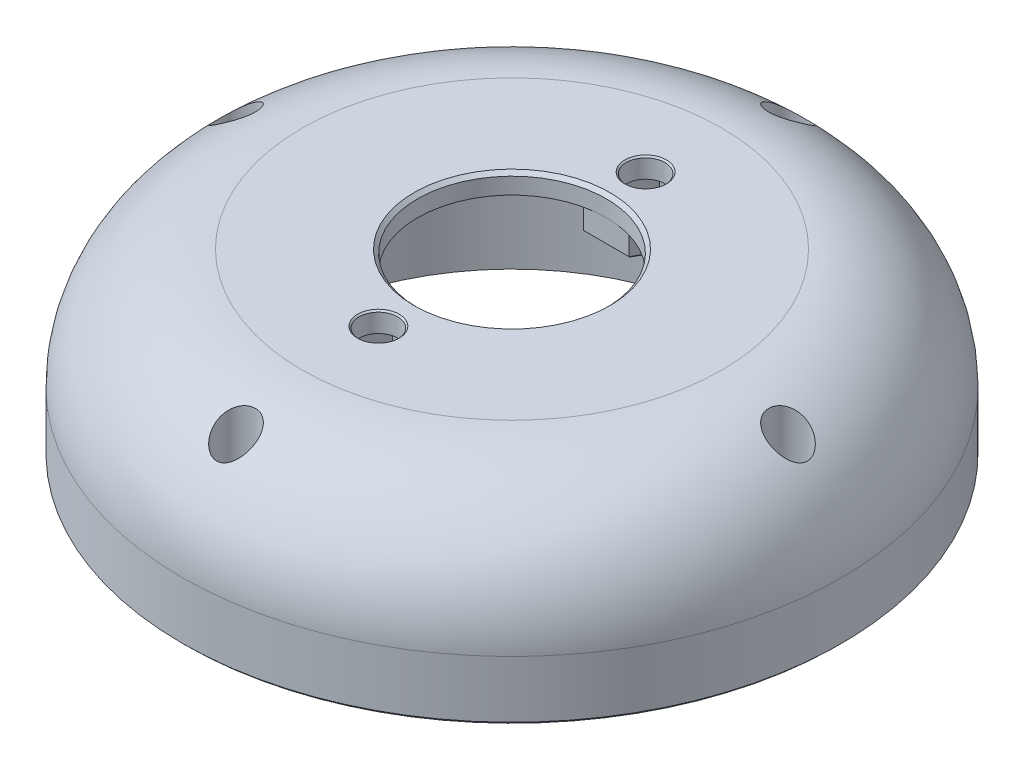
SolidWorks part; units mm, degrees
ref_plane "Front Plane" through (0, 0, 0) normal (0, 0, 1) x (1, 0, 0)
ref_plane "Top Plane" through (0, 0, 0) normal (0, 1, 0) x (1, 0, 0)
ref_plane "Right Plane" through (0, 0, 0) normal (1, 0, 0) x (0, 0, -1)
sketch "Sketch1" plane through (0, 0, 0) normal (0, 1, 0) x (1, 0, 0)
  circle A0 centre (0, 0) radius 11.5
  circle A1 centre (0, 0) radius 16.5
  dimension "D1" = 5
  dimension "D2" = 33
extrude "Boss-Extrude1" add sketch "Sketch1" along normal blind 8
sketch "Sketch2" plane through (0, 8, 0) normal (0, 1, 0) x (1, 0, 0)
  circle A0 centre (0, 0) radius 16.5
extrude "Boss-Extrude2" add sketch "Sketch2" along normal blind 1
scale "Scale1" scale about centroid uniform scaling yes scale factor 1.666667
sketch "Sketch3" plane through (0, 11.7467, 0) normal (0, 1, 0) x (1, 0, 0)
  line L0 (0, 13) -> (0, 11.15)
  line L1 (0, -12.95) -> (0, -11.15)
  line L10 (0, 11.15) -> (0, 0)
  line L11 (0, 0) -> (0, -11.15)
  circle A0 centre (0, 0) radius 7.875
  circle A4 centre (0, 11.15) radius 1.6125
  circle A5 centre (0, -11.15) radius 1.6125
  dimension "D1" = 15.75
  dimension "D8" = 3.225
  dimension "D9" = 1.8
  dimension "D10" = 3.225
  dimension "D2" = 11.15
  dimension "D3" = 11.15
extrude "Cut-Extrude1" cut sketch "Sketch3" against normal blind 9.65 contours A0 | A4 | A5 | A0 | A4 | A5 region at (0.6844, 11.7467, -11.15) region at (0.6844, 11.7467, 11.15) region at (-3.3423, 11.7467, 0)
chamfer "Chamfer2" distance 0.125 angle 45 2 edges at (0, 11.7467, -9.5375) (0, 11.7467, 12.7625)
chamfer "Chamfer4" distance 0.25 angle 45 1 edges at (0, -3.2533, 27.5)
sketch "Sketch4" plane through (0, 11.7467, 0) normal (0, 1, 0) x (1, 0, 0)
  circle A0 centre (23.03, 0) radius 1.6125
  circle A1 centre (0, 23.03) radius 1.6125
  circle A2 centre (0, -23.03) radius 1.6125
  circle A3 centre (-23.03, 0) radius 1.6125
  point P11 (0, 0)
  dimension "D2" = 3.225
  dimension "D1" = 4
extrude "Cut-Extrude2" cut sketch "Sketch4" against normal through all
chamfer "Chamfer6" distance 0.3 angle 45 1 edges at (0, 11.7467, 7.875)
chamfer "Chamfer7" distance 0.125 angle 45 4 edges at (-23.03, 11.7467, 1.6125) (0, 11.7467, 24.6425) (23.03, 11.7467, 1.6125) (0, 11.7467, -21.4175)
fillet "Fillet1" radius 10 1 edges at (0, 11.7467, 27.5)
sketch "Sketch5" plane through (0, 10.08, 0) normal (0, -1, 0) x (1, 0, 0)
  line L0 (-3.7816, 11.15) -> (-1.8908, 7.875)
  line L1 (-3.2043, 11.15) -> (-1.6021, 8.375)
  line L2 (-1.6021, 8.375) -> (1.6021, 8.375)
  line L3 (1.6021, 8.375) -> (3.2043, 11.15)
  line L4 (3.2043, 11.15) -> (1.6021, 13.925)
  line L5 (1.6021, 13.925) -> (-1.6021, 13.925)
  line L6 (-1.6021, 13.925) -> (-3.2043, 11.15)
  line L7 (3.2043, -11.15) -> (1.6021, -8.375)
  line L8 (1.6021, -8.375) -> (-1.6021, -8.375)
  line L9 (-1.6021, -8.375) -> (-3.2043, -11.15)
  line L10 (-3.2043, -11.15) -> (-1.6021, -13.925)
  line L11 (-1.6021, -13.925) -> (1.6021, -13.925)
  line L12 (1.6021, -13.925) -> (3.2043, -11.15)
  line L13 (-1.8908, 7.875) -> (1.8908, 7.875)
  line L14 (1.8908, 7.875) -> (3.7816, 11.15)
  line L15 (3.7816, 11.15) -> (1.8908, 14.425)
  line L16 (1.8908, 14.425) -> (-1.8908, 14.425)
  line L17 (-1.8908, 14.425) -> (-3.7816, 11.15)
  line L18 (3.7816, -11.15) -> (1.8908, -7.875)
  line L19 (1.8908, -7.875) -> (-1.8908, -7.875)
  line L20 (-1.8908, -7.875) -> (-3.7816, -11.15)
  line L21 (-3.7816, -11.15) -> (-1.8908, -14.425)
  line L22 (-1.8908, -14.425) -> (1.8908, -14.425)
  line L23 (1.8908, -14.425) -> (3.7816, -11.15)
  circle A0 centre (0, 11.15) radius 2.775 construction
  circle A1 centre (0, -11.15) radius 2.775 construction
  dimension "D1" = 5.55
  dimension "D2" = 5.55
  dimension "D3" = 0.5
  dimension "D4" = 0.5
extrude "Boss-Extrude3" add sketch "Sketch5" along normal blind 2
chamfer "Chamfer8" distance 0.125 angle 45 12 edges at (-2.8362, 8.08, 12.7875) (-2.8362, 8.08, 9.5125) (0, 8.08, 7.875) (2.8362, 8.08, 9.5125) (2.8362, 8.08, 12.7875) (0, 8.08, 14.425) (-2.4032, 8.08, 12.5375) (-2.4032, 8.08, 9.7625) (0, 8.08, 8.375) (2.4032, 8.08, 9.7625) (2.4032, 8.08, 12.5375) (0, 8.08, 13.925)
chamfer "Chamfer9" distance 0.125 angle 45 12 edges at (0, 8.08, -7.875) (2.8362, 8.08, -9.5125) (2.8362, 8.08, -12.7875) (0, 8.08, -14.425) (-2.8362, 8.08, -12.7875) (-2.8362, 8.08, -9.5125) (-2.4032, 8.08, -9.7625) (-2.4032, 8.08, -12.5375) (0, 8.08, -13.925) (2.4032, 8.08, -12.5375) (2.4032, 8.08, -9.7625) (0, 8.08, -8.375)
